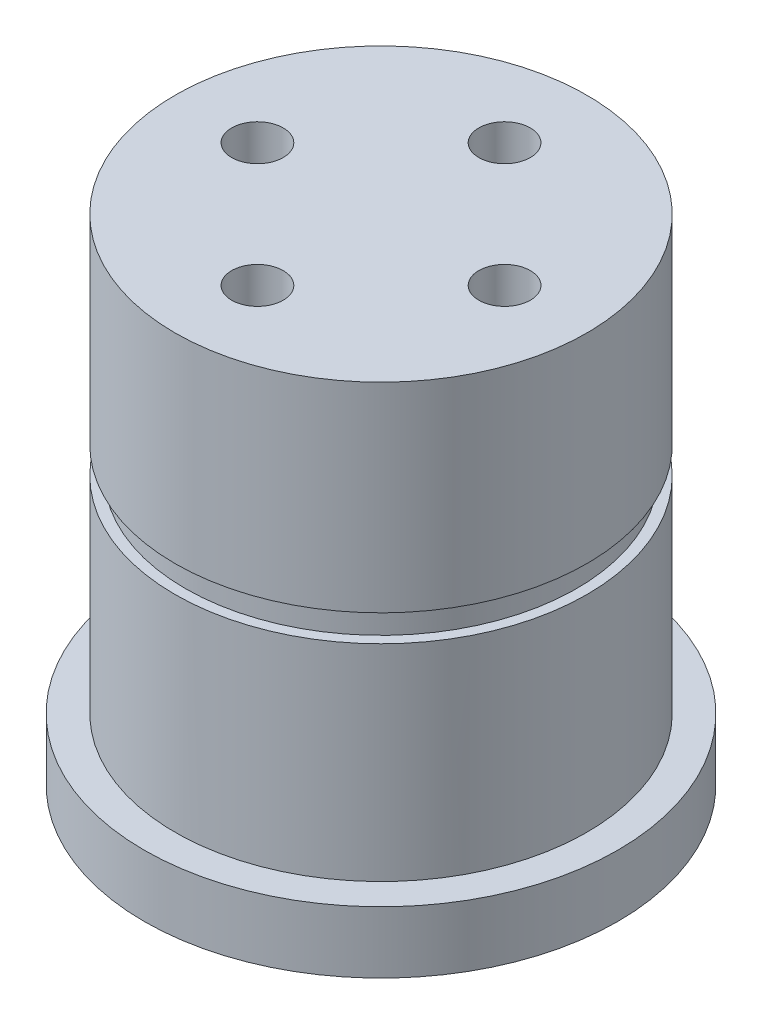
SolidWorks part; units mm, degrees
material "Сплав 2024"
ref_plane "Спереди" through (0, 0, 0) normal (0, 0, 1) x (1, 0, 0)
ref_plane "Сверху" through (0, 0, 0) normal (0, 1, 0) x (1, 0, 0)
ref_plane "Справа" through (0, 0, 0) normal (1, 0, 0) x (0, 0, -1)
sketch "Эскиз1" plane through (0, 0, 0) normal (0, 1, 0) x (1, 0, 0)
  circle A0 centre (0, 0) radius 10
  dimension "D1" = 20
extrude "Бобышка-Вытянуть1" add sketch "Эскиз1" along normal blind 24
sketch "Эскиз5" plane through (0, 0, 0) normal (0, -1, 0) x (1, 0, 0)
  line L0 (0, 10) -> (0, -10) construction
  line L1 (10, 0) -> (-10, 0) construction
  circle A1 centre (0, 0) radius 6 construction
  circle A2 centre (0, 0) radius 10 construction
  dimension "D1" = 12
hole_wizard "Отверстие обработанное метчиком M3x0.52" positions "Эскиз7" profile "Эскиз6" tap size "M3x0.5" standard "Ansi Metric"
sketch "Эскиз7" plane through (-4.8388, 24, -4.76) normal (0, -1, 0) x (-1, 0, 0)
  line L2 (-4.8388, -14.76) -> (-4.8388, 5.24) construction
  line L4 (-14.8388, -4.76) -> (5.1612, -4.76) construction
  circle A0 centre (-4.8388, -4.76) radius 6 construction
  point P0 (-4.8388, 1.24)
  point P6 (-10.8388, -4.76)
  point P10 (-4.8388, -10.76)
  point P12 (1.1612, -4.76)
sketch "Эскиз6" plane through (0, 24, -6) normal (1, 0, 0) x (0, 0, 1)
  line L0 (0, 0) -> (0, 9.2511)
  line L1 (0, 9.2511) -> (1.25, 8.5)
  line L2 (1.25, 8.5) -> (1.25, 0)
  line L5 (1.25, 0) -> (0, 0)
  line L10 (0, 9.2511) -> (-1.25, 8.5) construction
  line L11 (0, -6.35) -> (0, 107.95) construction
  dimension "Диаметр сверла" = 2.5
  dimension "Глубина сверла" = 8.5
  dimension "Угол заточки сверла" = 118
cosmetic thread "Отверстие резьбы1" parameters "D1"=6, "D2"=3
cosmetic thread "Отверстие резьбы2" parameters "D1"=6, "D2"=3
cosmetic thread "Отверстие резьбы3" parameters "D1"=6, "D2"=3
cosmetic thread "Отверстие резьбы4" parameters "D1"=6, "D2"=3
ref_plane "Плоскость2" through (0, 3, 0) normal (0, -1, 0) x (-1, 0, 0)
sketch "Эскиз10" plane through (0, 3, 0) normal (0, -1, 0) x (-1, 0, 0)
  circle A0 centre (0, 0) radius 11.5
  circle A2 centre (0, 0) radius 10
  circle A3 centre (0, 0) radius 10 construction
  dimension "D1" = 23
extrude "Бобышка-Вытянуть2" add sketch "Эскиз10" along normal up to surface (3 mm away) up to face at (0, 0, 10)
ref_plane "Плоскость1" through (0, 13, 0) normal (0, 1, 0) x (1, 0, 0)
sketch "Эскиз8" plane through (0, 13, 0) normal (0, 1, 0) x (1, 0, 0)
  circle A0 centre (0, 0) radius 10
  circle A1 centre (0, 0) radius 10 construction
  circle A3 centre (0, 0) radius 9.5
  dimension "D1" = 19
extrude "Вырез-Вытянуть1" cut sketch "Эскиз8" along normal blind 1.3
